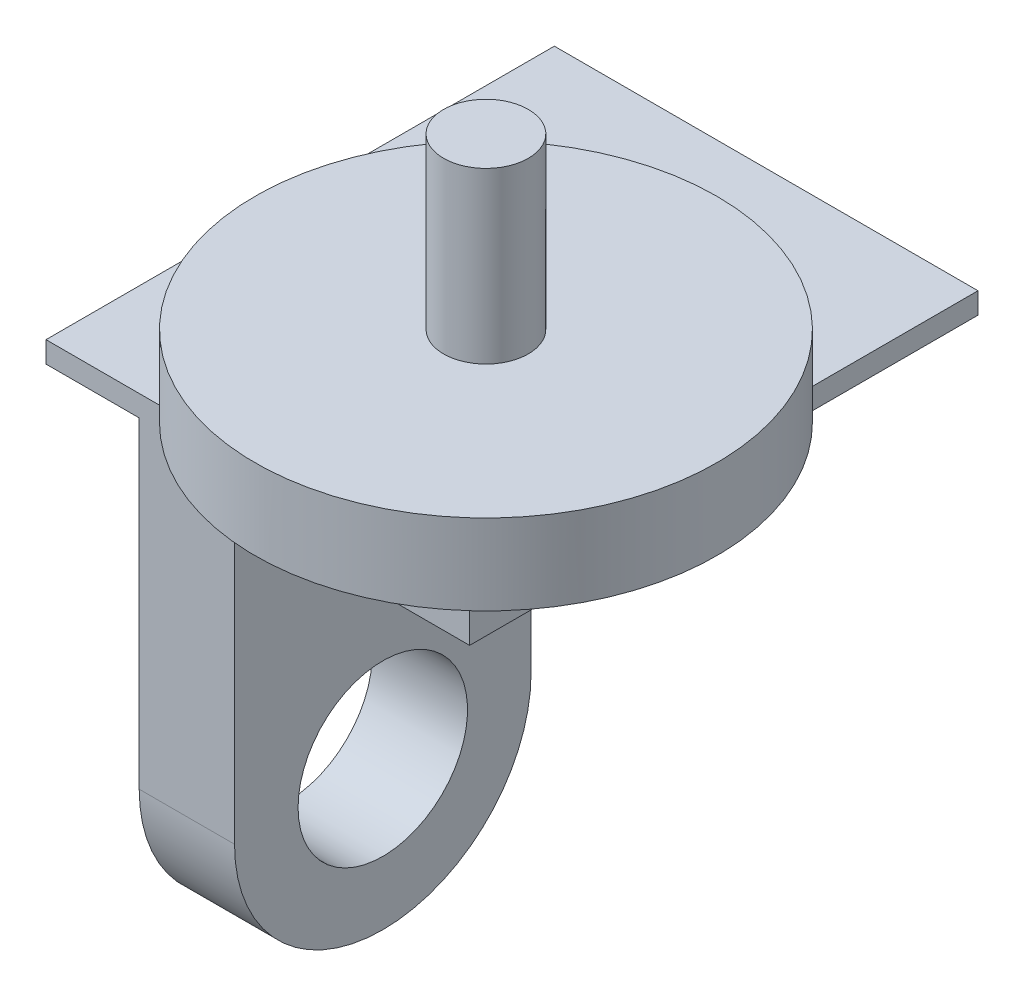
SolidWorks part; units mm, degrees
ref_plane "Piano frontale" through (0, 0, 0) normal (0, 0, 1) x (1, 0, 0)
ref_plane "Piano superiore" through (0, 0, 0) normal (0, 1, 0) x (1, 0, 0)
ref_plane "Piano destro" through (0, 0, 0) normal (1, 0, 0) x (0, 0, -1)
sketch "Schizzo1" plane through (0, 0, 0) normal (1, 0, 0) x (0, 0, -1)
  line L0 (-826.3993, 0) -> (40493.5669, 0) construction
  line L1 (0, -826.3993) -> (0, 40493.5669) construction
  line L2 (-70, 0) -> (-70, 136.8)
  line L3 (-70, 136.8) -> (70, 136.8)
  line L4 (70, 136.8) -> (70, 0)
  circle A0 centre (0, 0) radius 40
  arc A1 (-70, 0) -> (70, 0) centre (0, 0) ccw
  dimension "D1" = 70
  dimension "D2" = 80
  dimension "D3" = 136.8
extrude "Estrusione-Estrusione1" add sketch "Schizzo1" along normal blind 45
sketch "Schizzo2" plane through (0, 136.8, 0) normal (0, 1, 0) x (1, 0, 0)
  line L0 (-1000, 0) -> (49000, 0) construction
  line L1 (93.7, -996.2442) -> (93.7, 49003.7558) construction
  line L6 (45, -70) -> (0, -70) construction
  line L7 (0, 70) -> (156, 70)
  line L8 (0, 70) -> (0, -70)
  line L9 (0, -70) -> (156, -70)
  line L10 (156, 70) -> (156, -70)
  circle A0 centre (93.7, 0) radius 30 construction
  dimension "D1" = 93.7
  dimension "D2" = 156
  dimension "D3" = 60
extrude "Estrusione-Estrusione2" add sketch "Schizzo2" along normal blind 25
sketch "Schizzo5" plane through (0, 161.8, 0) normal (0, 1, 0) x (1, 0, 0)
  line L1 (0, -70) -> (-44, -70)
  line L2 (0, -70) -> (0, 70)
  line L3 (156, 170) -> (-44, 170)
  line L4 (-44, -70) -> (-44, 170)
  line L5 (-44, 170) -> (156, 170)
  line L6 (-44, 170) -> (-44, -70)
  line L7 (0, 70) -> (156, 70)
  line L8 (156, 170) -> (156, 70)
  line M8 (0, 70) -> (0, -70)
  line M11 (156, 70) -> (0, 70)
  dimension "D1" = 200
  dimension "D2" = 240
extrude "Estrusione-Estrusione4" add sketch "Schizzo5" against normal blind 10 contours L8 L3 L4 L1 M8 M11 region at (37.633, 161.8, -91.7431)
ref_plane "Piano1" through (93.7, 0, 0) normal (1, 0, 0) x (0, 0, -1)
sketch "Schizzo7" plane through (93.7, 0, 0) normal (1, 0, 0) x (0, 0, -1)
  line L0 (0, -1000) -> (0, 49000) construction
  line L1 (0, 131.8) -> (48, 131.8)
  line L2 (48, 131.8) -> (48, 136.8)
  line L3 (70, 136.8) -> (-70, 136.8) construction
  line L4 (48, 136.8) -> (30, 136.8)
  line L6 (0, 279.8) -> (20, 279.8)
  line L7 (20, 279.8) -> (20, 199.8)
  line L8 (20, 199.8) -> (109, 199.8)
  line L9 (109, 199.8) -> (109, 161.8)
  line L10 (-70, 161.8) -> (170, 161.8) construction
  line L11 (109, 161.8) -> (30, 161.8)
  line L12 (30, 161.8) -> (30, 136.8)
  line L13 (0, 131.8) -> (0, 279.8)
  dimension "D1" = 20
  dimension "D2" = 80
  dimension "D3" = 109
  dimension "D4" = 38
  dimension "D5" = 5
  dimension "D6" = 48
  dimension "D7" = 30
revolve "Rivoluzione1" add sketch "Schizzo7" angle 360 about L0
ref_axis "Assi1" through (93.7, 285.5235, 0) along (0, -1, 0)
ref_point "Punto1"
